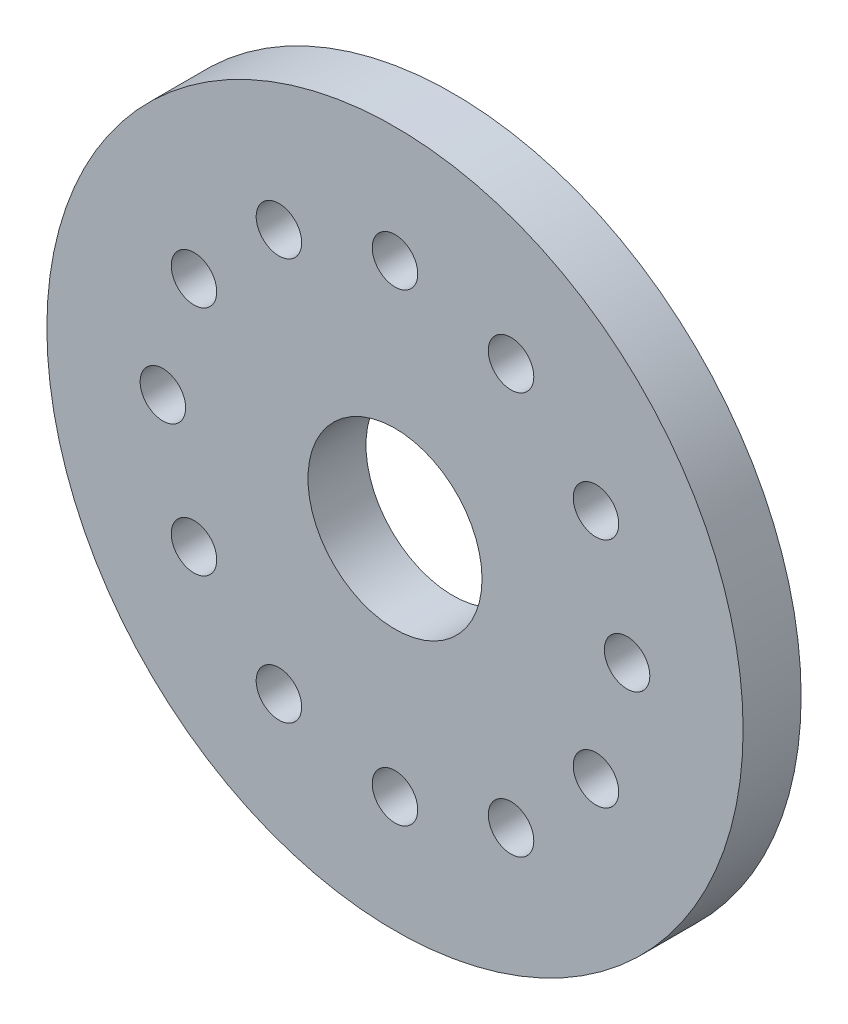
SolidWorks part; units mm, degrees
material "PC High Viscosity"
ref_plane "Front Plane" through (0, 0, 0) normal (0, 0, 1) x (1, 0, 0)
ref_plane "Top Plane" through (0, 0, 0) normal (0, 1, 0) x (1, 0, 0)
ref_plane "Right Plane" through (0, 0, 0) normal (1, 0, 0) x (0, 0, -1)
sketch "Sketch1" plane through (0, 0, 0) normal (0, 0, 1) x (1, 0, 0)
  circle A0 centre (0, 0) radius 9.525
  circle A1 centre (0, 0) radius 38.1
  circle A2 centre (0, 25.4) radius 2.4892
  circle A3 centre (12.7, 21.997) radius 2.4892
  circle A4 centre (21.997, 12.7) radius 2.4892
  circle A5 centre (25.4, 0) radius 2.4892
  circle A6 centre (21.997, -12.7) radius 2.4892
  circle A7 centre (12.7, -21.997) radius 2.4892
  circle A8 centre (0, -25.4) radius 2.4892
  circle A9 centre (-12.7, -21.997) radius 2.4892
  circle A10 centre (-21.997, -12.7) radius 2.4892
  circle A11 centre (-25.4, 0) radius 2.4892
  circle A12 centre (-21.997, 12.7) radius 2.4892
  circle A13 centre (-12.7, 21.997) radius 2.4892
  circle A14 centre (0, 0) radius 25.4 construction
  point P30 (0, 0)
  dimension "D1" = 19.05
  dimension "D2" = 25.4
  dimension "D3" = 4.9784
  dimension "D5" = 12.7
  dimension "D4" = 12
extrude "Boss-Extrude1" add sketch "Sketch1" along normal blind 6.35
